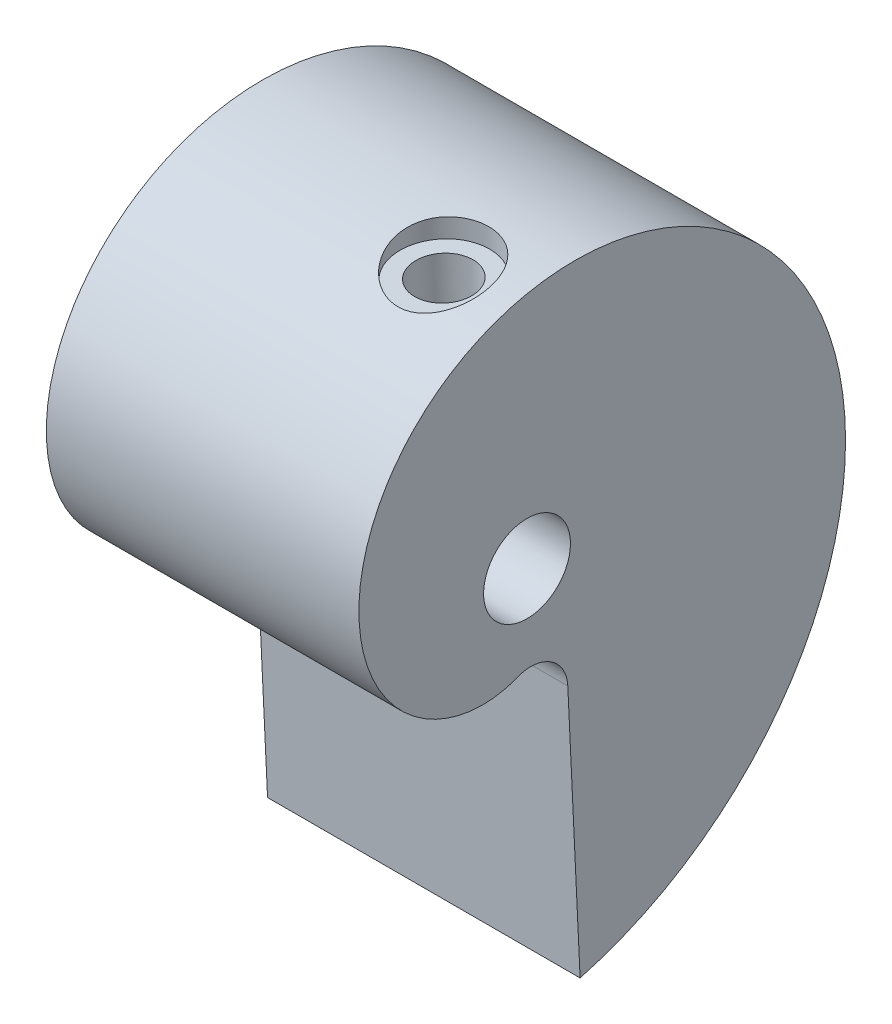
SolidWorks part; units mm, degrees
ref_plane "Front" through (0, 0, 0) normal (0, 0, 1) x (1, 0, 0)
ref_plane "Top" through (0, 0, 0) normal (0, 1, 0) x (1, 0, 0)
ref_plane "Right" through (0, 0, 0) normal (1, 0, 0) x (0, 0, -1)
ref_axis "side-side" through (80.9, 0, 0) along (-1, 0, 0)
ref_axis "up-down" through (0, 50, 0) along (0, -1, 0)
ref_axis "front-back" through (0, 0, -80.9) along (0, 0, 1)
sketch "Sketch1" plane through (0, 0, 0) normal (1, 0, 0) x (0, 0, -1)
  line L1 (0, 0) -> (1.2764, 14.5892) construction
  line L3 (0, -6.048) -> (3.9328, -22.9766) construction
  line L4 (-0.7563, -6.1729) -> (4.3472, -4.4405) construction
  line L5 (0, 50) -> (0, -50) construction
  line L6 (0, 0) -> (-0.7563, -6.1729) construction
  line L7 (0, 0) -> (0, 8.3256) construction
  line L8 (0, 0) -> (3.9328, -22.9766) construction
  circle A1 centre (0, 0) radius 3
  arc A3 (2.3518, -8.3323) -> (-0.7563, -6.1729) centre (0, -8.4008) ccw
  arc A5 (2.3518, -8.3323) -> (3.9328, -22.9766) centre (96.292, -5.5976) ccw
  arc A6 (0, -6.048) -> (-3.0432, -5.2266) centre (0, 0) cw construction
  arc A7 (3.9328, -22.9766) -> (7.5421, -22.057) centre (0, 0) ccw construction
  dimension "D1" = 17.2628
  dimension "D3" = 173.015
  dimension "D2" = 71.25
  dimension "D4" = 170.287
sketch "Sketch2" plane through (0, 0, 0) normal (1, 0, 0) x (0, 0, -1)
  circle A0 centre (0, 0) radius 6.219
curve "Helix/Spiral1"
sketch "Sketch3" plane through (0, 0, 0) normal (1, 0, 0) x (0, 0, -1)
  line L0 (3.667, -26.3255) -> (2.8165, -8.4312)
  line L2 (0.2592, -8.5528) -> (0.8772, -28.9476) construction
  line L4 (0, 0) -> (8.8177, 0) construction
  line L5 (-0.7915, -6.1995) -> (0, 0) construction
  arc A0 (2.3518, -8.3323) -> (3.9328, -22.9766) centre (96.292, -5.5976) ccw construction
  circle A1 centre (0, 0) radius 28.9609 construction
  circle A3 centre (0, 0) radius 26.5797 construction
  arc A4 (2.8165, -8.4312) -> (-0.7008, -6.1794) centre (0.2592, -8.5528) ccw
  spline S0 degree 3 poles (-1798.7666, -874.3921) (7.5291, 165.7669) (24.686, -8.4914) (-4.5554, -6.5417) (-5.645, -6.2371) (-7.7173, -5.107) (-8.6984, -4.2811) (-10.3118, -2.1646) (-10.9425, -0.8744) (-11.6475, 2.0069) (-11.7204, 3.5968) (-11.1828, 6.8263) (-10.5713, 8.4643) (-9.132, 10.7343) (-8.5662, 11.4596) (-7.2731, 12.8101) (-6.5459, 13.4352) (-4.9487, 14.5497) (-4.0788, 15.0392) (-2.2227, 15.8507) (-1.2366, 16.1728) (0.8187, 16.6232) (1.8877, 16.7515) (4.0697, 16.7948) (5.1825, 16.7098) (7.4086, 16.3151) (8.5219, 16.0053) (10.7026, 15.1584) (11.7701, 14.6212) (13.8126, 13.3267) (14.7874, 12.5693) (16.5989, 10.8509) (17.4355, 9.89) (18.9279, 7.7907) (19.5836, 6.6524) (20.6771, 4.2334) (21.1147, 2.9528) (21.7416, 0.2921) (21.9308, -1.0879) (22.0389, -3.8984) (21.9579, -5.3288) (21.5138, -8.1861) (21.1507, -9.613) (20.1414, -12.4071) (19.4952, -13.7742) (17.9301, -16.3919) (17.0111, -17.6424) (14.9223, -19.9722) (13.7524, -21.0514) (11.1943, -22.9879) (9.8063, -23.8452) (-50.5924, -53.4906) (-249.0866, 129.7172) (1061.5848, 1654.1982) knots -1.648876 -1.648876 -1.648876 -1.648876 0.0625 0.0625 0.125 0.125 0.1875 0.1875 0.25 0.25 0.3125 0.3125 0.375 0.375 0.40625 0.40625 0.4375 0.4375 0.46875 0.46875 0.5 0.5 0.53125 0.53125 0.5625 0.5625 0.59375 0.59375 0.625 0.625 0.65625 0.65625 0.6875 0.6875 0.71875 0.71875 0.75 0.75 0.78125 0.78125 0.8125 0.8125 0.84375 0.84375 0.875 0.875 0.90625 0.90625 0.9375 0.9375 0.96875 0.96875 2.216576 2.216576 2.216576 2.216576 only from (-0.7008, -6.1794) to (3.667, -26.3255) construction
  spline S1 degree 3 poles (-0.7008, -6.1794) (-1.5251, -6.5128) (-2.4949, -6.679) (-4.5554, -6.5417) (-5.645, -6.2371) (-7.7173, -5.107) (-8.6984, -4.2811) (-10.3118, -2.1646) (-10.9425, -0.8744) (-11.6475, 2.0069) (-11.7204, 3.5968) (-11.1828, 6.8263) (-10.5713, 8.4643) (-9.132, 10.7343) (-8.5662, 11.4596) (-7.2731, 12.8101) (-6.5459, 13.4352) (-4.9487, 14.5497) (-4.0788, 15.0392) (-2.2227, 15.8507) (-1.2366, 16.1728) (0.8187, 16.6232) (1.8877, 16.7515) (4.0697, 16.7948) (5.1825, 16.7098) (7.4086, 16.3151) (8.5219, 16.0053) (10.7026, 15.1584) (11.7701, 14.6212) (13.8126, 13.3267) (14.7874, 12.5693) (16.5989, 10.8509) (17.4355, 9.89) (18.9279, 7.7907) (19.5836, 6.6524) (20.6771, 4.2334) (21.1147, 2.9528) (21.7416, 0.2921) (21.9308, -1.0879) (22.0389, -3.8984) (21.9579, -5.3288) (21.5138, -8.1861) (21.1507, -9.613) (20.1414, -12.4071) (19.4952, -13.7742) (17.9301, -16.3919) (17.0111, -17.6424) (14.9223, -19.9722) (13.7524, -21.0514) (11.1943, -22.9879) (9.8063, -23.8452) (6.855, -25.2938) (5.2918, -25.885) (3.667, -26.3255) knots 0 0 0 0 0.0625 0.0625 0.125 0.125 0.1875 0.1875 0.25 0.25 0.3125 0.3125 0.375 0.375 0.40625 0.40625 0.4375 0.4375 0.46875 0.46875 0.5 0.5 0.53125 0.53125 0.5625 0.5625 0.59375 0.59375 0.625 0.625 0.65625 0.65625 0.6875 0.6875 0.71875 0.71875 0.75 0.75 0.78125 0.78125 0.8125 0.8125 0.84375 0.84375 0.875 0.875 0.90625 0.90625 0.9375 0.9375 0.96875 0.96875 1 1 1 1
  dimension "D1" = 2.5602
  dimension "D5" = 2.3813
  dimension "D2" = 262.724
  dimension "D3" = 17.4246
  dimension "D4" = 2.413
  dimension "D6" = 20.3948
sketch "Sketch4" plane through (0, 0, 0) normal (1, 0, 0) x (0, 0, -1)
  line L0 (3.667, -26.3255) -> (2.8165, -8.4312) construction
  line L1 (3.667, -26.3255) -> (2.8165, -8.4312)
  arc A1 (2.8165, -8.4312) -> (-0.7008, -6.1794) centre (0.2592, -8.5528) ccw construction
  arc A2 (2.8165, -8.4312) -> (-0.7008, -6.1794) centre (0.2592, -8.5528) ccw
  circle A3 centre (0, 0) radius 3
  spline S0 degree 3 poles (-2660.2075, -1382.1612) (1.8841, 217.6042) (28.6066, -8.7529) (-4.5554, -6.5417) (-5.645, -6.2371) (-7.7173, -5.107) (-8.6984, -4.2811) (-10.3118, -2.1646) (-10.9425, -0.8744) (-11.6475, 2.0069) (-11.7204, 3.5968) (-11.1828, 6.8263) (-10.5713, 8.4643) (-9.132, 10.7343) (-8.5662, 11.4596) (-7.2731, 12.8101) (-6.5459, 13.4352) (-4.9487, 14.5497) (-4.0788, 15.0392) (-2.2227, 15.8507) (-1.2366, 16.1728) (0.8187, 16.6232) (1.8877, 16.7515) (4.0697, 16.7948) (5.1825, 16.7098) (7.4086, 16.3151) (8.5219, 16.0053) (10.7026, 15.1584) (11.7701, 14.6212) (13.8126, 13.3267) (14.7874, 12.5693) (16.5989, 10.8509) (17.4355, 9.89) (18.9279, 7.7907) (19.5836, 6.6524) (20.6771, 4.2334) (21.1147, 2.9528) (21.7416, 0.2921) (21.9308, -1.0879) (22.0389, -3.8984) (21.9579, -5.3288) (21.5138, -8.1861) (21.1507, -9.613) (20.1414, -12.4071) (19.4952, -13.7742) (17.9301, -16.3919) (17.0111, -17.6424) (14.9223, -19.9722) (13.7524, -21.0514) (11.1943, -22.9879) (9.8063, -23.8452) (-59.0847, -57.6589) (-309.2023, 186.9338) (1727.2749, 2400.3169) knots -1.886716 -1.886716 -1.886716 -1.886716 0.0625 0.0625 0.125 0.125 0.1875 0.1875 0.25 0.25 0.3125 0.3125 0.375 0.375 0.40625 0.40625 0.4375 0.4375 0.46875 0.46875 0.5 0.5 0.53125 0.53125 0.5625 0.5625 0.59375 0.59375 0.625 0.625 0.65625 0.65625 0.6875 0.6875 0.71875 0.71875 0.75 0.75 0.78125 0.78125 0.8125 0.8125 0.84375 0.84375 0.875 0.875 0.90625 0.90625 0.9375 0.9375 0.96875 0.96875 2.39642 2.39642 2.39642 2.39642 only from (-0.7008, -6.1794) to (3.667, -26.3255) construction
  spline S1 degree 3 poles (-0.7008, -6.1794) (-1.5251, -6.5128) (-2.4949, -6.679) (-4.5554, -6.5417) (-5.645, -6.2371) (-7.7173, -5.107) (-8.6984, -4.2811) (-10.3118, -2.1646) (-10.9425, -0.8744) (-11.6475, 2.0069) (-11.7204, 3.5968) (-11.1828, 6.8263) (-10.5713, 8.4643) (-9.132, 10.7343) (-8.5662, 11.4596) (-7.2731, 12.8101) (-6.5459, 13.4352) (-4.9487, 14.5497) (-4.0788, 15.0392) (-2.2227, 15.8507) (-1.2366, 16.1728) (0.8187, 16.6232) (1.8877, 16.7515) (4.0697, 16.7948) (5.1825, 16.7098) (7.4086, 16.3151) (8.5219, 16.0053) (10.7026, 15.1584) (11.7701, 14.6212) (13.8126, 13.3267) (14.7874, 12.5693) (16.5989, 10.8509) (17.4355, 9.89) (18.9279, 7.7907) (19.5836, 6.6524) (20.6771, 4.2334) (21.1147, 2.9528) (21.7416, 0.2921) (21.9308, -1.0879) (22.0389, -3.8984) (21.9579, -5.3288) (21.5138, -8.1861) (21.1507, -9.613) (20.1414, -12.4071) (19.4952, -13.7742) (17.9301, -16.3919) (17.0111, -17.6424) (14.9223, -19.9722) (13.7524, -21.0514) (11.1943, -22.9879) (9.8063, -23.8452) (6.855, -25.2938) (5.2918, -25.885) (3.667, -26.3255) knots 0 0 0 0 0.0625 0.0625 0.125 0.125 0.1875 0.1875 0.25 0.25 0.3125 0.3125 0.375 0.375 0.40625 0.40625 0.4375 0.4375 0.46875 0.46875 0.5 0.5 0.53125 0.53125 0.5625 0.5625 0.59375 0.59375 0.625 0.625 0.65625 0.65625 0.6875 0.6875 0.71875 0.71875 0.75 0.75 0.78125 0.78125 0.8125 0.8125 0.84375 0.84375 0.875 0.875 0.90625 0.90625 0.9375 0.9375 0.96875 0.96875 1 1 1 1
  point P0 (3.6309, -26.3255)
  point P5 (-0.7008, -6.1794)
  dimension "D1" = 6
extrude "Boss-Extrude1" add sketch "Sketch4" along normal blind 21.59
sketch "Sketch5" plane through (0, 0, 0) normal (1, 0, 0) x (0, 0, -1)
  line L0 (3.9633, -26.2433) -> (5.4294, -25.8274)
  line L1 (3.9633, -26.2433) -> (6.0428, -33.5741)
  spline S0 degree 3 poles (3.667, -26.3255) (5.2918, -25.885) (6.855, -25.2938) (9.8063, -23.8452) (11.1943, -22.9879) (13.7524, -21.0514) (14.9223, -19.9722) (17.0111, -17.6424) (17.9301, -16.3919) (19.4952, -13.7742) (20.1414, -12.4071) (21.1507, -9.613) (21.5138, -8.1861) (21.9579, -5.3288) (22.0389, -3.8984) (21.9308, -1.0879) (21.7416, 0.2921) (21.1147, 2.9528) (20.6771, 4.2334) (19.5836, 6.6524) (18.9279, 7.7907) (17.4355, 9.89) (16.5989, 10.8509) (14.7874, 12.5693) (13.8126, 13.3267) (11.7701, 14.6212) (10.7026, 15.1584) (8.5219, 16.0053) (7.4086, 16.3151) (5.1825, 16.7098) (4.0697, 16.7948) (1.8877, 16.7515) (0.8187, 16.6232) (-1.2366, 16.1728) (-2.2227, 15.8507) (-4.0788, 15.0392) (-4.9487, 14.5497) (-6.5459, 13.4352) (-7.2731, 12.8101) (-8.5662, 11.4596) (-9.132, 10.7343) (-10.5713, 8.4643) (-11.1828, 6.8263) (-11.7204, 3.5968) (-11.6475, 2.0069) (-10.9425, -0.8744) (-10.3118, -2.1646) (-8.6984, -4.2811) (-7.7173, -5.107) (-5.645, -6.2371) (-4.5554, -6.5417) (-2.4949, -6.679) (-1.5251, -6.5128) (-0.7008, -6.1794) knots 0 0 0 0 0.03125 0.03125 0.0625 0.0625 0.09375 0.09375 0.125 0.125 0.15625 0.15625 0.1875 0.1875 0.21875 0.21875 0.25 0.25 0.28125 0.28125 0.3125 0.3125 0.34375 0.34375 0.375 0.375 0.40625 0.40625 0.4375 0.4375 0.46875 0.46875 0.5 0.5 0.53125 0.53125 0.5625 0.5625 0.59375 0.59375 0.625 0.625 0.6875 0.6875 0.75 0.75 0.8125 0.8125 0.875 0.875 0.9375 0.9375 1 1 1 1 construction
  point P4 (3.667, -26.3255)
  point P5 (0, 0)
  point P9 (13.4127, -21.2724)
  point P10 (3.9633, -26.2433)
  dimension "D1" = 7.62
  dimension "D2" = 1.524
  dimension "D3" = 3.3493
  dimension "D4" = 26.3287
sketch "Sketch6" plane through (0, 0, 0) normal (1, 0, 0) x (0, 0, -1)
  circle A0 centre (0, -9.3938) radius 2.3812 construction
  circle A1 centre (0, 0) radius 5.9965 construction
  circle A3 centre (0, 0) radius 9.3938 construction
  arc A4 (2.8165, -8.4312) -> (-0.7008, -6.1794) centre (0.2592, -8.5528) ccw construction
  circle A5 centre (0, 0) radius 7.0125 construction
  dimension "D1" = 4.7625
  dimension "D2" = 1.016
sketch3d "3DSketch1"
  circle A3 centre (21.645, -5.3684, 5.9313) radius 1.6026
  circle A4 centre (21.645, 0, 0) radius 11
  circle A5 centre (14.895, 0, 0) radius 11
  point P10 (20.0424, -5.3684, 5.9313)
  point P12 (10.645, 0, 0)
  point P14 (3.895, 0, 0)
ref_plane "Plane1" through (0, 0, 0) normal (0, -0.9989, -0.0475) x (-1, 0, 0)
sketch "Sketch8" plane through (0, 0, 0) normal (0, -0.9989, -0.0475) x (1, 0, 0)
  line L0 (21.645, -11) -> (21.645, 11) construction
  line L2 (80.9, 0) -> (-80.9, 0) construction
  circle A0 centre (16.565, 0) radius 3.175
  point P4 (0, 0)
  dimension "D1" = 6.35
  dimension "D2" = 5.08
extrude "Cut-Extrude1" cut sketch "Sketch8" against normal blind 5.08 from offset 15.24 offset against normal yes
hole_wizard "#10-32 Tapped Hole1" positions "Sketch9" profile "Sketch10" tap size "#10-32" standard "ANSI Inch"
sketch "Sketch9" plane through (0, 15.2228, 0.7236) normal (0, 0.9989, 0.0475) x (1, 0, 0)
  point P0 (16.565, 0)
sketch "Sketch10" plane through (16.565, 15.2228, 0.7236) normal (1, 0, 0) x (0, -0.0475, 0.9989)
  line L0 (0, 0) -> (0, 15.0309)
  line L1 (0, 15.0309) -> (2.0193, 13.8176)
  line L2 (2.0193, 13.8176) -> (2.0193, 0)
  line L5 (2.0193, 0) -> (0, 0)
  line L10 (0, 15.0309) -> (-2.0193, 13.8176) construction
  line L11 (0, -6.35) -> (0, 107.95) construction
  dimension "Tap Drill Dia." = 4.0386
  dimension "Tap Drill Depth" = 13.8176
  dimension "Drill Angle" = 118
